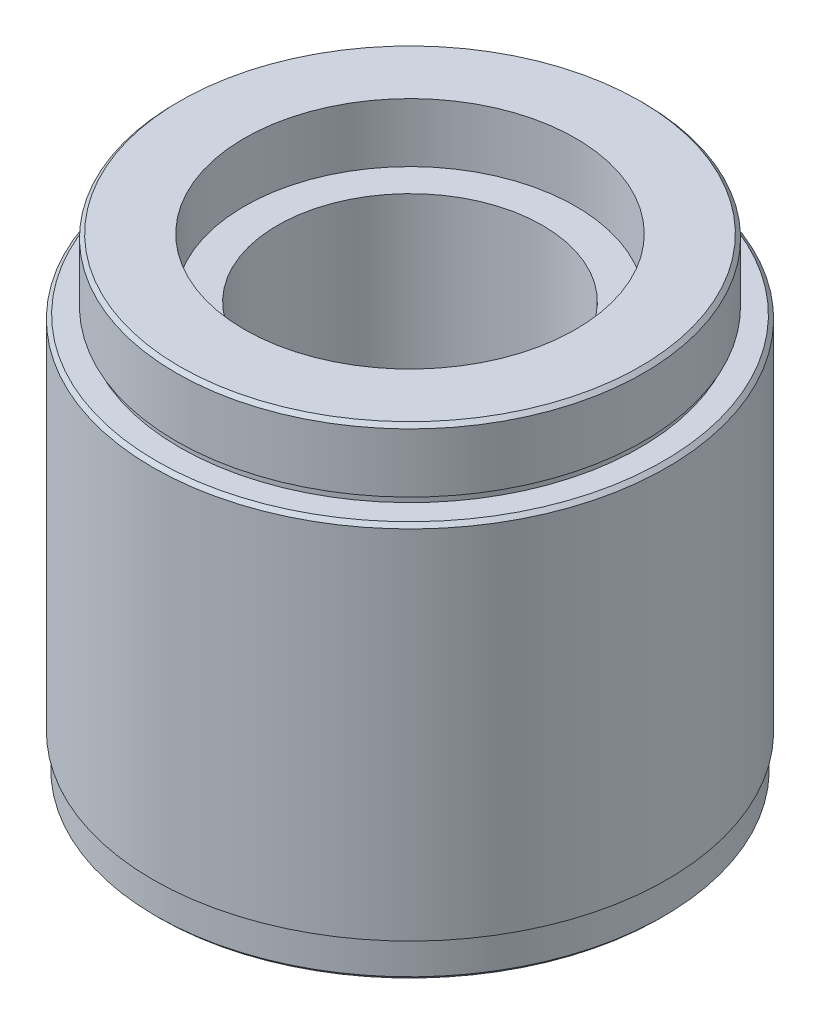
SolidWorks part; units mm, degrees
ref_plane "Front Plane" through (0, 0, 0) normal (0, 0, 1) x (1, 0, 0)
ref_plane "Top Plane" through (0, 0, 0) normal (0, 1, 0) x (1, 0, 0)
ref_plane "Right Plane" through (0, 0, 0) normal (1, 0, 0) x (0, 0, -1)
sketch "Sketch1" plane through (0, 0, 0) normal (0, 1, 0) x (1, 0, 0)
  circle A0 centre (0, 0) radius 34.925
extrude "Main Body" add sketch "Sketch1" along normal blind 63.5 separate body
sketch "Sketch2" plane through (0, 0, 0) normal (0, -1, 0) x (1, 0, 0)
  circle A0 centre (0, 0) radius 34.5
extrude "Bottom Step" cut sketch "Sketch2" against normal blind 5 flip side to cut
sketch "Sketch3" plane through (0, 63.5, 0) normal (0, 1, 0) x (1, 0, 0)
  circle A0 centre (0, 0) radius 31.75
extrude "Top Diameter" cut sketch "Sketch3" against normal blind 9.52 flip side to cut
sketch "Sketch4" plane through (0, 53.98, 0) normal (0, 1, 0) x (1, 0, 0)
  circle A0 centre (0, 0) radius 31.25
extrude "Cut-Extrude3" cut sketch "Sketch4" along normal blind 1 flip side to cut
sketch "Sketch5" plane through (0, 63.5, 0) normal (0, 1, 0) x (1, 0, 0)
  circle A0 centre (0, 0) radius 22.5
extrude "Insert Bore" cut sketch "Sketch5" against normal blind 8
sketch "Sketch6" plane through (0, 0, 0) normal (0, -1, 0) x (1, 0, 0)
  circle A0 centre (0, 0) radius 18
extrude "Cut-Extrude5" cut sketch "Sketch6" against normal through all
sketch "Sketch7" plane through (0, 0, 0) normal (0, -1, 0) x (1, 0, 0)
  circle A0 centre (0, 0) radius 21
extrude "Cut-Extrude6" cut sketch "Sketch7" against normal blind 5
chamfer "Bottom Edge Chamfer" distance 0.5 angle 45 1 edges at (0, 0, -34.5) first distance on face at (0, 0, -21)
chamfer "Top Face Chamfer" distance 0.5 angle 45 1 edges at (0, 63.5, 31.75) first distance on face at (0, 63.5, 22.5)
chamfer "Body To Top Face Chamfer" distance 0.5 angle 45 1 edges at (0, 53.98, 34.925) first distance on face at (0, 53.98, 34.925)
